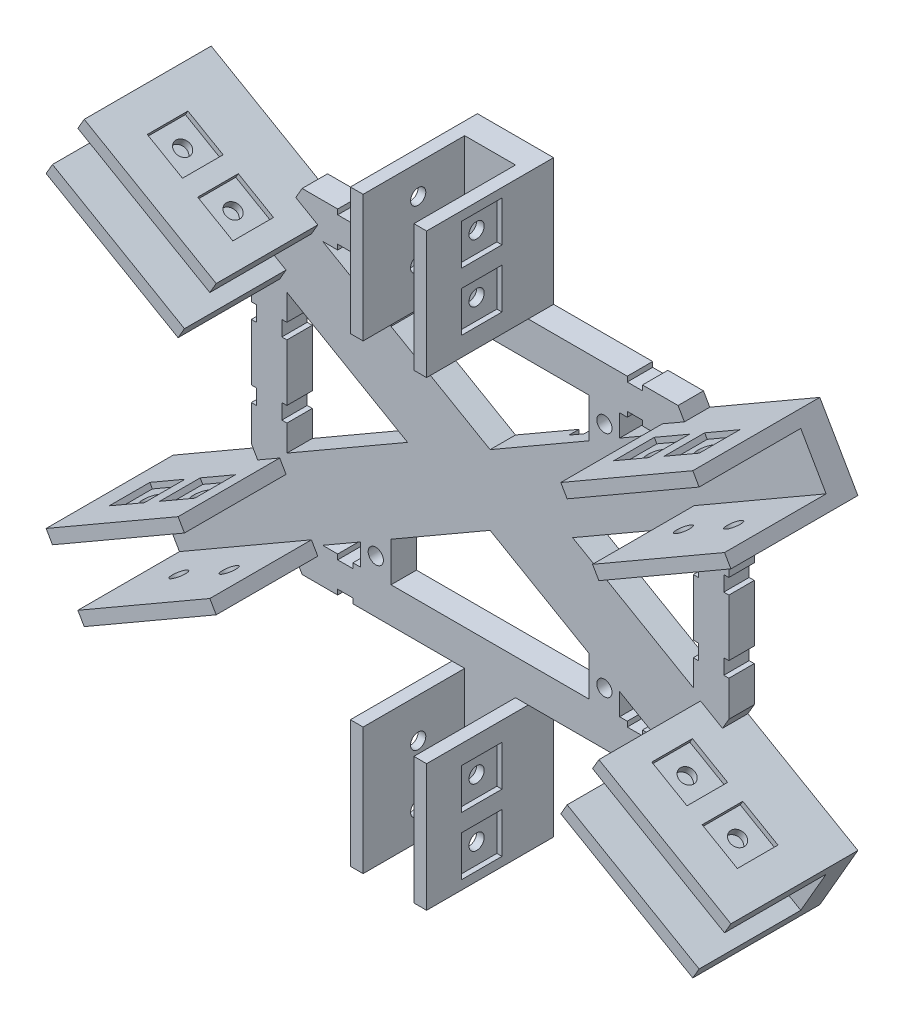
SolidWorks part; units mm, degrees
ref_plane "Plan de face" through (0, 0, 0) normal (0, 0, 1) x (1, 0, 0)
ref_plane "Plan de dessus" through (0, 0, 0) normal (0, 1, 0) x (1, 0, 0)
ref_plane "Plan de droite" through (0, 0, 0) normal (1, 0, 0) x (0, 0, -1)
sketch "Esquisse1" plane through (0, 0, 0) normal (0, 0, 1) x (1, 0, 0)
  line L1 (-27, -32.909) -> (-27, -31.909)
  line L2 (-27, -31.909) -> (-30, -31.909)
  line L3 (-30, -31.909) -> (-30, -32.909)
  line L4 (-30, -32.909) -> (-37, -32.909)
  line L5 (89.9983, 57.7339) -> (33.4379, 25.0787) construction
  line L6 (-47, -15.5885) -> (-47, -8.5885)
  line L7 (-47, -8.5885) -> (-46, -8.5885)
  line L8 (-46, -8.5885) -> (-46, -5.5885)
  line L9 (-46, -5.5885) -> (-47, -5.5885)
  line L10 (-47, -5.5885) -> (-47, 5.5885)
  line L11 (0, -32.909) -> (0, 32.909) construction
  line L12 (40, 0) -> (-40, 0) construction
  line L13 (-42, -24.2487) -> (0, 0) construction
  line L14 (-40, 5.5885) -> (-40, -5.5885)
  line L15 (-40, -5.5885) -> (-41, -5.5885)
  line L16 (-41, -5.5885) -> (-41, -8.5885)
  line L17 (-41, -8.5885) -> (-40, -8.5885)
  line L18 (-40, -8.5885) -> (-40, -13.7128)
  line L19 (40, 13.7128) -> (16.2487, 0)
  line L20 (-32.9585, -25.909) -> (-30, -25.909)
  line L21 (-30, -25.909) -> (-30, -26.909)
  line L22 (-30, -26.909) -> (-27, -26.909)
  line L23 (-27, -26.909) -> (-27, -25.909)
  line L24 (59.9007, 43.2438) -> (38.2501, 30.7438)
  line L25 (-42, 24.2487) -> (0, 0) construction
  line L26 (19.5, -25.909) -> (0, -25.909)
  line L27 (-27, 26.909) -> (-27, 25.909)
  line L28 (-30, 26.909) -> (-27, 26.909)
  line L29 (-30, 25.909) -> (-30, 26.909)
  line L30 (-32.9585, 25.909) -> (-30, 25.909)
  line L31 (-40, 13.7128) -> (-16.2487, 0)
  line L32 (-40, 8.5885) -> (-40, 13.7128)
  line L33 (-41, 8.5885) -> (-40, 8.5885)
  line L34 (-41, 5.5885) -> (-41, 8.5885)
  line L35 (-40, 5.5885) -> (-41, 5.5885)
  line L36 (-46, 5.5885) -> (-47, 5.5885)
  line L37 (-46, 8.5885) -> (-46, 5.5885)
  line L38 (-47, 8.5885) -> (-46, 8.5885)
  line L39 (-47, 15.5885) -> (-47, 8.5885)
  line L40 (-59.9007, 43.2438) -> (-38.2501, 30.7438)
  line L41 (-30, 32.909) -> (-37, 32.909)
  line L42 (-30, 31.909) -> (-30, 32.909)
  line L43 (-27, 31.909) -> (-30, 31.909)
  line L44 (-27, 32.909) -> (-27, 31.909)
  line L45 (-27, 32.909) -> (-7.5, 32.909)
  line L46 (42, 24.2487) -> (0, 0) construction
  line L47 (42, -24.2487) -> (0, 0) construction
  line L48 (27, 32.909) -> (27, 31.909)
  line L49 (27, 31.909) -> (30, 31.909)
  line L50 (30, 31.909) -> (30, 32.909)
  line L51 (30, 32.909) -> (37, 32.909)
  line L52 (-45.7501, 17.7534) -> (-47, 15.5885)
  line L53 (47, 15.5885) -> (47, 8.5885)
  line L54 (47, 8.5885) -> (46, 8.5885)
  line L55 (46, 8.5885) -> (46, 5.5885)
  line L56 (46, 5.5885) -> (47, 5.5885)
  line L57 (40, 5.5885) -> (41, 5.5885)
  line L58 (41, 5.5885) -> (41, 8.5885)
  line L59 (41, 8.5885) -> (40, 8.5885)
  line L60 (40, 8.5885) -> (40, 13.7128)
  line L61 (32.9585, 25.909) -> (25.5, 21.6028)
  line L62 (32.9585, 25.909) -> (30, 25.909)
  line L63 (30, 25.909) -> (30, 26.909)
  line L64 (30, 26.909) -> (27, 26.909)
  line L65 (27, 26.909) -> (27, 25.909)
  line L66 (27, -26.909) -> (27, -25.909)
  line L67 (30, -26.909) -> (27, -26.909)
  line L68 (30, -25.909) -> (30, -26.909)
  line L69 (32.9585, -25.909) -> (30, -25.909)
  line L70 (-32.9585, 25.909) -> (-25.5, 21.6028)
  line L71 (40, -8.5885) -> (40, -13.7128)
  line L72 (41, -8.5885) -> (40, -8.5885)
  line L73 (41, -5.5885) -> (41, -8.5885)
  line L74 (40, -5.5885) -> (41, -5.5885)
  line L75 (40, 5.5885) -> (40, -5.5885)
  line L76 (47, -5.5885) -> (47, 5.5885)
  line L77 (46, -5.5885) -> (47, -5.5885)
  line L78 (46, -8.5885) -> (46, -5.5885)
  line L79 (47, -8.5885) -> (46, -8.5885)
  line L80 (47, -15.5885) -> (47, -8.5885)
  line L81 (-37, 32.909) -> (-38.2501, 30.7438)
  line L82 (30, -32.909) -> (37, -32.909)
  line L83 (30, -31.909) -> (30, -32.909)
  line L84 (27, -31.909) -> (30, -31.909)
  line L85 (27, -32.909) -> (27, -31.909)
  line L86 (40, -13.7128) -> (16.2487, 0)
  line L87 (-25.5, 25.909) -> (-25.5, 21.6028)
  line L88 (-19.5, 25.909) -> (-19.5, 18.1387)
  line L89 (-40, -13.7128) -> (-16.2487, 0)
  line L90 (25.5, 25.909) -> (25.5, 21.6028)
  line L91 (19.5, 25.909) -> (19.5, 18.1387)
  line L92 (19.5, 18.1387) -> (0, 6.8803)
  line L93 (-19.5, 18.1387) -> (0, 6.8803)
  line L94 (-32.9585, -25.909) -> (-25.5, -21.6028)
  line L95 (-25.5, -25.909) -> (-25.5, -21.6028)
  line L96 (-19.5, -25.909) -> (-19.5, -18.1387)
  line L97 (-19.5, -18.1387) -> (0, -6.8803)
  line L98 (32.9585, -25.909) -> (25.5, -21.6028)
  line L99 (25.5, -25.909) -> (25.5, -21.6028)
  line L100 (19.5, -25.909) -> (19.5, -18.1387)
  line L101 (19.5, -18.1387) -> (0, -6.8803)
  line L102 (27, 25.909) -> (25.5, 25.909)
  line L103 (19.5, 25.909) -> (0, 25.909)
  line L104 (0, 25.909) -> (-19.5, 25.909)
  line L105 (-25.5, 25.909) -> (-27, 25.909)
  line L106 (0, -25.909) -> (-19.5, -25.909)
  line L107 (-25.5, -25.909) -> (-27, -25.909)
  line L108 (27, -25.909) -> (25.5, -25.909)
  line L109 (67.4007, 30.2534) -> (59.9007, 43.2438)
  line L110 (67.4007, 30.2534) -> (45.7501, 17.7534)
  line L111 (37, 32.909) -> (38.2501, 30.7438)
  line L112 (45.7501, 17.7534) -> (47, 15.5885)
  line L113 (-67.4007, 30.2534) -> (-45.7501, 17.7534)
  line L114 (-67.4007, 30.2534) -> (-59.9007, 43.2438)
  line L115 (-7.5, 32.909) -> (-7.5, 57.909)
  line L116 (-7.5, 57.909) -> (7.5, 57.909)
  line L117 (37, -32.909) -> (38.2501, -30.7438)
  line L118 (45.7501, -17.7534) -> (47, -15.5885)
  line L119 (67.4007, -30.2534) -> (45.7501, -17.7534)
  line L120 (67.4007, -30.2534) -> (59.9007, -43.2438)
  line L121 (59.9007, -43.2438) -> (38.2501, -30.7438)
  line L122 (-37, -32.909) -> (-38.2501, -30.7438)
  line L123 (-45.7501, -17.7534) -> (-47, -15.5885)
  line L124 (-67.4007, -30.2534) -> (-59.9007, -43.2438)
  line L125 (-67.4007, -30.2534) -> (-45.7501, -17.7534)
  line L126 (-59.9007, -43.2438) -> (-38.2501, -30.7438)
  line L127 (7.5, 57.909) -> (7.5, 32.909)
  line L128 (7.5, 32.909) -> (27, 32.909)
  line L129 (7.5, -32.909) -> (27, -32.909)
  line L130 (-27, -32.909) -> (-7.5, -32.909)
  line L131 (-7.5, -32.909) -> (-7.5, -57.909)
  line L132 (7.5, -57.909) -> (7.5, -32.909)
  line L133 (-7.5, -57.909) -> (7.5, -57.909)
  circle A0 centre (22.5, 22.5) radius 1.5
  circle A1 centre (-22.5, 22.5) radius 1.5
  circle A2 centre (22.5, -22.5) radius 1.5
  circle A3 centre (-22.5, -22.5) radius 1.5
  point P10 (-42, -24.2487)
  point P41 (-47, 0)
  point P73 (0, 25.909)
  point P74 (0, -25.909)
  point P75 (0, -25.909)
  point P94 (47, 0)
  dimension "D13" = 2
  dimension "D1" = 1
  dimension "D2" = 3
  dimension "D3" = 7
  dimension "D4" = 3
  dimension "D5" = 7
  dimension "D6" = 60
  dimension "D7" = 15
  dimension "D8" = 1
  dimension "D9" = 1
  dimension "D10" = 1
  dimension "D11" = 7
  dimension "D12" = 3
  dimension "D14" = 20
  dimension "D15" = 30
  dimension "D16" = 2
  dimension "D17" = 22.5
  dimension "D18" = 22.5
  dimension "D19" = 3
  dimension "D20" = 90
  dimension "D21" = 90
  dimension "D22" = 2.5
  dimension "D23" = 7.5
  dimension "D24" = 7.5
  dimension "D25" = 25
extrude "Boss.-Extru.2" add sketch "Esquisse1" along normal blind 5
sketch "Esquisse4" plane through (0, 0, 0) normal (0, 0, -1) x (-1, 0, 0)
  line L1 (-22.5, 20.1429) -> (-20.4587, 21.3214)
  line L2 (-20.4587, 21.3214) -> (-20.4587, 23.6786)
  line L3 (-20.4587, 23.6786) -> (-22.5, 24.8571)
  line L4 (-22.5, 24.8571) -> (-24.5413, 23.6786)
  line L5 (-24.5413, 23.6786) -> (-24.5413, 21.3214)
  line L6 (-24.5413, 21.3214) -> (-22.5, 20.1429)
  line L7 (0, -32.2873) -> (0, 32.2873) construction
  line L8 (43.6304, 0) -> (-43.6304, 0) construction
  line L9 (0, -32.909) -> (0, 32.909) construction
  line L10 (-40, 0) -> (40, 0) construction
  line L11 (24.5413, 21.3214) -> (22.5, 20.1429)
  line L12 (24.5413, 23.6786) -> (24.5413, 21.3214)
  line L13 (22.5, 24.8571) -> (24.5413, 23.6786)
  line L14 (20.4587, 23.6786) -> (22.5, 24.8571)
  line L15 (20.4587, 21.3214) -> (20.4587, 23.6786)
  line L16 (22.5, 20.1429) -> (20.4587, 21.3214)
  line L17 (22.5, -20.1429) -> (20.4587, -21.3214)
  line L18 (20.4587, -21.3214) -> (20.4587, -23.6786)
  line L19 (20.4587, -23.6786) -> (22.5, -24.8571)
  line L20 (22.5, -24.8571) -> (24.5413, -23.6786)
  line L21 (24.5413, -23.6786) -> (24.5413, -21.3214)
  line L22 (24.5413, -21.3214) -> (22.5, -20.1429)
  line L23 (-24.5413, -21.3214) -> (-22.5, -20.1429)
  line L24 (-24.5413, -23.6786) -> (-24.5413, -21.3214)
  line L25 (-22.5, -24.8571) -> (-24.5413, -23.6786)
  line L26 (-20.4587, -23.6786) -> (-22.5, -24.8571)
  line L27 (-20.4587, -21.3214) -> (-20.4587, -23.6786)
  line L28 (-22.5, -20.1429) -> (-20.4587, -21.3214)
  circle A0 centre (-22.5, 22.5) radius 2.0413 construction
  circle A1 centre (22.5, 22.5) radius 2.0413 construction
  circle A2 centre (22.5, -22.5) radius 2.0413 construction
  circle A3 centre (-22.5, -22.5) radius 2.0413 construction
extrude "Enlèv. mat.-Extru.2" cut sketch "Esquisse4" against normal blind 2
sketch "Esquisse5" plane through (63.6506, 36.7487, 0) normal (0.866, 0.5, 0) x (0, 0, -1)
  line L0 (-5, -7.5001) -> (-5, -5.0001)
  line L2 (-5, -5.0001) -> (-25, -5.0001)
  line L3 (-25, -5.0001) -> (-25, -7.5001)
  line L4 (-25, -7.5001) -> (-5, -7.5001)
  dimension "D1" = 20
  dimension "D2" = 2.5
extrude "Boss.-Extru.3" add sketch "Esquisse5" against normal blind 30
sketch "Esquisse7" plane through (63.6506, 36.7487, 0) normal (0.866, 0.5, 0) x (0, 0, -1)
  line L0 (-5, 4.9999) -> (-5, 7.4999)
  line L2 (-5, 7.4999) -> (-25, 7.4999)
  line L3 (-25, 7.4999) -> (-25, 4.9999)
  line L4 (-25, 4.9999) -> (-5, 4.9999)
  line L5 (-5, -5.0001) -> (-5, 7.4999) construction
  dimension "D1" = 20
  dimension "D2" = 2.5
extrude "Boss.-Extru.4" add sketch "Esquisse7" against normal blind 30
sketch "Esquisse8" plane through (3.7501, -6.4953, 0) normal (0.5, -0.866, 0) x (0.866, 0.5, 0)
  line L1 (47.611, 18.1555) -> (55.611, 18.1555)
  line L2 (47.611, 18.1555) -> (47.611, 10.1555)
  line L3 (47.611, 10.1555) -> (55.611, 10.1555)
  line L4 (55.611, 18.1555) -> (55.611, 10.1555)
  dimension "D1" = 8
  dimension "D2" = 8
extrude "Enlèv. mat.-Extru.3" cut sketch "Esquisse8" against normal blind 1
sketch "Esquisse9" plane through (3.7501, -6.4953, 0) normal (0.5, -0.866, 0) x (0.866, 0.5, 0)
  line L0 (55.611, 18.1555) -> (47.611, 18.1555) construction
  line L1 (59.0628, 18.1555) -> (67.0628, 18.1555)
  line L2 (59.0628, 18.1555) -> (59.0628, 10.1555)
  line L3 (59.0628, 10.1555) -> (67.0628, 10.1555)
  line L4 (67.0628, 18.1555) -> (67.0628, 10.1555)
  dimension "D1" = 8
  dimension "D2" = 8
extrude "Enlèv. mat.-Extru.4" cut sketch "Esquisse9" against normal blind 1
ref_plane "Plan8" through (0.0001, -0.0001, 0) normal (-0.5, 0.866, 0) x (-0.866, -0.5, 0)
sketch "Esquisse10" plane through (3.2501, -5.6293, 0) normal (0.5, -0.866, 0) x (0.866, 0.5, 0)
  line L3 (55.611, 18.1555) -> (47.611, 18.1555) construction
  line L4 (47.611, 18.1555) -> (47.611, 10.1555) construction
  circle A0 centre (51.611, 14.1555) radius 1.5
  point P2 (51.611, 18.1555)
  point P3 (47.611, 14.1555)
extrude "Enlèv. mat.-Extru.5" cut sketch "Esquisse10" against normal blind 3
ref_plane "Plan9" through (49.6552, 28.6684, 0) normal (-0.866, -0.5, 0) x (0, 0, 1)
mirror "Symétrie4" about plane through (49.6552, 28.6684, 0) normal (-0.866, -0.5, 0) of "Enlèv. mat.-Extru.5"
mirror "Symétrie5" about plane through (0.0001, -0.0001, 0) normal (-0.5, 0.866, 0) of "Enlèv. mat.-Extru.3", "Enlèv. mat.-Extru.4", "Enlèv. mat.-Extru.5", "Symétrie4"
mirror "Symétrie7" about plane through (0, 0, 0) normal (0, 1, 0) of "Boss.-Extru.3", "Boss.-Extru.4", "Enlèv. mat.-Extru.3", "Enlèv. mat.-Extru.4", "Enlèv. mat.-Extru.5", "Symétrie4", "Symétrie5"
mirror "Symétrie8" about plane through (0, 0, 0) normal (1, 0, 0) of "Boss.-Extru.3", "Boss.-Extru.4", "Enlèv. mat.-Extru.3", "Enlèv. mat.-Extru.4", "Symétrie5", "Symétrie4", "Enlèv. mat.-Extru.5", "Symétrie7"
sketch "Esquisse11" plane through (0, 57.909, 0) normal (0, 1, 0) x (1, 0, 0)
  line L6 (-7.5, -5) -> (-5, -5)
  line L7 (-7.5, -5) -> (-7.5, -25)
  line L8 (-7.5, -25) -> (-5, -25)
  line L9 (-5, -5) -> (-5, -25)
  dimension "D1" = 2.5
  dimension "D2" = 20
extrude "Boss.-Extru.5" add sketch "Esquisse11" against normal blind 25
sketch "Esquisse50" plane through (-7.5, 26.5177, -42.9653) normal (-1, 0, 0) x (0, 0, 1)
  line L0 (42.9653, 31.3912) -> (42.9653, 6.3912) construction
  line L1 (53.1253, 18.1555) -> (61.1253, 18.1555)
  line L2 (53.1253, 18.1555) -> (53.1253, 10.1555)
  line L3 (53.1253, 10.1555) -> (61.1253, 10.1555)
  line L4 (61.1253, 18.1555) -> (61.1253, 10.1555)
  dimension "D1" = 8
  dimension "D2" = 8
  dimension "D3" = 10.16
extrude "Enlèv. mat.-Extru.25" cut sketch "Esquisse50" against normal blind 1
sketch "Esquisse52" plane through (-7.5, 26.5177, -42.9653) normal (-1, 0, 0) x (0, 0, 1)
  line L0 (53.1253, 18.1555) -> (53.1253, 10.1555) construction
  line L1 (53.1253, 29.6055) -> (61.1253, 29.6055)
  line L2 (53.1253, 29.6055) -> (53.1253, 21.6055)
  line L3 (53.1253, 21.6055) -> (61.1253, 21.6055)
  line L4 (61.1253, 29.6055) -> (61.1253, 21.6055)
  line L6 (61.1253, 18.1555) -> (53.1253, 18.1555) construction
  dimension "D1" = 8
  dimension "D2" = 8
  dimension "D3" = 3.45
extrude "Enlèv. mat.-Extru.26" cut sketch "Esquisse52" against normal blind 1
sketch "Esquisse54" plane through (-6.5, 26.5177, -42.9653) normal (-1, 0, 0) x (0, 0, 1)
  line L3 (61.1253, 18.1555) -> (53.1253, 18.1555) construction
  line L4 (53.1253, 18.1555) -> (53.1253, 10.1555) construction
  circle A0 centre (57.1253, 14.1555) radius 1.5
  point P2 (57.1253, 18.1555)
  point P3 (53.1253, 14.1555)
extrude "Enlèv. mat.-Extru.27" cut sketch "Esquisse54" against normal blind 3
ref_plane "Plan14" through (0, 46.3982, 0) normal (0, 1, 0) x (-1, 0, 0)
mirror "Symétrie9" about plane through (0, 46.3982, 0) normal (0, 1, 0) of "Enlèv. mat.-Extru.27"
ref_plane "Plan17" through (0, 0, 0) normal (-1, 0, 0) x (0, 0, 1)
mirror "Symétrie10" about plane through (0, 0, 0) normal (-1, 0, 0) of "Symétrie9", "Enlèv. mat.-Extru.27", "Enlèv. mat.-Extru.26", "Enlèv. mat.-Extru.25", "Boss.-Extru.5"
mirror "Symétrie11" about plane through (0, 0, 0) normal (0, 1, 0) of "Symétrie10", "Symétrie9", "Enlèv. mat.-Extru.27", "Enlèv. mat.-Extru.26", "Enlèv. mat.-Extru.25", "Boss.-Extru.5"
sketch "Esquisse55" plane through (0, -25.909, 0) normal (0, 1, 0) x (0.866, 0, 0.5)
  line L0 (-6.875, 11.9078) -> (6.875, -11.9078) construction
  line L1 (10.8253, 6.25) -> (13.4234, 7.75)
  line L2 (10.8253, 6.25) -> (11.8253, 4.5179)
  line L3 (11.8253, 4.5179) -> (14.4234, 6.0179)
  line L4 (13.4234, 7.75) -> (14.4234, 6.0179)
  line L5 (-16.8875, -9.75) -> (16.8875, 9.75) construction
  line L7 (0.4703, -0.8147) -> (2.9703, -5.1448) construction
  line L8 (-13.4234, -7.75) -> (-12.4234, -9.4821)
  line L9 (-9.8253, -7.9821) -> (-12.4234, -9.4821)
  line L10 (-10.8253, -6.25) -> (-9.8253, -7.9821)
  line L11 (-10.8253, -6.25) -> (-13.4234, -7.75)
  point P6 (13.3056, 1.7413)
  point P8 (0.4703, -0.8147)
  point P9 (-38.8182, 7.9371)
  point P10 (-26.4638, 21.0702)
  dimension "D1" = 3
  dimension "D2" = 2
  dimension "D3" = 12.5
extrude "Enlèv. mat.-Extru.28" cut sketch "Esquisse55" along normal blind 50
